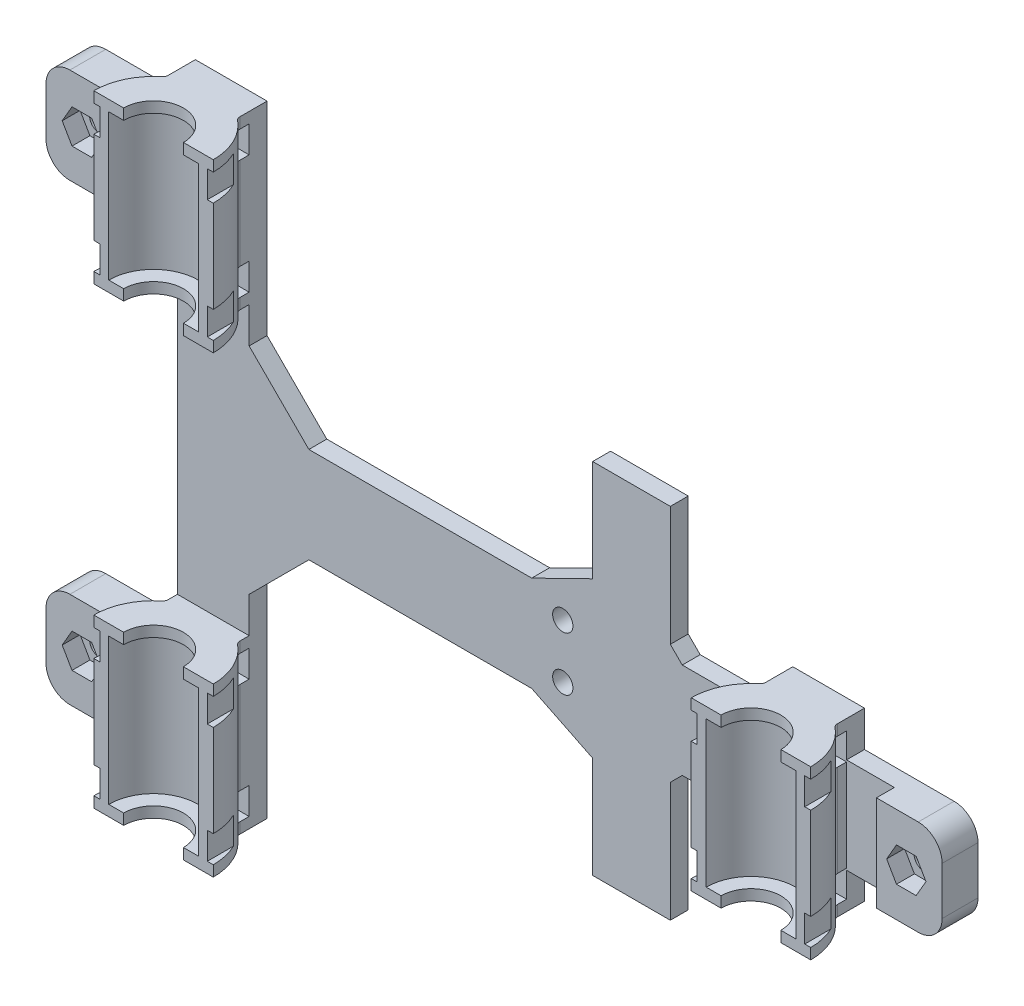
SolidWorks part; units mm, degrees
ref_plane "前视基准面" through (0, 0, 0) normal (0, 0, 1) x (1, 0, 0)
ref_plane "上视基准面" through (0, 0, 0) normal (0, 1, 0) x (1, 0, 0)
ref_plane "右视基准面" through (0, 0, 0) normal (1, 0, 0) x (0, 0, -1)
sketch "草图1" plane through (0, 0, 0) normal (0, 0, 1) x (1, 0, 0)
  line L1 (75, -70) -> (-75, -70)
  line L2 (75, -70) -> (75, 70)
  line L3 (75, 70) -> (-75, 70)
  line L4 (-75, -70) -> (-75, 70)
  line L5 (75, -70) -> (-75, 70) construction
  line L6 (75, 70) -> (-75, -70) construction
  point P0 (0, 0)
  dimension "D1" = 150
  dimension "D2" = 140
extrude "凸台-拉伸1" add sketch "草图1" along normal blind 3
sketch "草图2" plane through (0, 0, 0) normal (0, 1, 0) x (1, 0, 0)
  line L0 (-1000, 0) -> (49000, 0) construction
  line L1 (-999.3205, -17) -> (49000.6795, -17) construction
  line L2 (0, -1000) -> (0, 49000) construction
  line L3 (-57.5, -13) -> (-60, -13)
  line L4 (-42.5, -13) -> (-40, -13)
  line L5 (-55, -13) -> (-57.5, -13)
  line L6 (-45, -13) -> (-42.5, -13)
  line L7 (-50, -1013) -> (-50, 48987) construction
  line L8 (-56, -5) -> (-56, -3)
  line L9 (-75, -3) -> (75, -3) construction
  line L10 (-44, -5) -> (-44, -3)
  line L11 (-56, -3) -> (-44, -3)
  line L12 (56, -3) -> (44, -3)
  line L13 (44, -5) -> (44, -3)
  line L14 (56, -5) -> (56, -3)
  line L15 (45, -13) -> (42.5, -13)
  line L16 (55, -13) -> (57.5, -13)
  line L17 (42.5, -13) -> (40, -13)
  line L18 (57.5, -13) -> (60, -13)
  line L19 (75, -3) -> (-75, -3) construction
  circle A0 centre (50, -13) radius 4 construction
  circle A1 centre (-50, -13) radius 4 construction
  circle A2 centre (-50, -13) radius 7.5 construction
  circle A3 centre (50, -13) radius 7.5 construction
  arc A4 (-57.5, -13) -> (-42.5, -13) centre (-50, -13) cw
  arc A5 (-60, -13) -> (-40, -13) centre (-50, -13) cw
  arc A6 (-55, -13) -> (-45, -13) centre (-50, -13) cw
  arc A7 (55, -13) -> (45, -13) centre (50, -13) ccw
  arc A8 (60, -13) -> (40, -13) centre (50, -13) ccw
  arc A9 (57.5, -13) -> (42.5, -13) centre (50, -13) ccw
  dimension "D3" = 10
  dimension "D2" = 15
  dimension "D4" = 5
  dimension "D6" = 8
  dimension "D1" = 17
  dimension "D5" = 12
  dimension "D7" = 100
  dimension "D8" = 14
extrude "凸台-拉伸2" add sketch "草图2" along normal blind 14 and the other way blind 14 contours A8 L14 L12 L13 | A9 L18 A8 L17 | A8 L12 L13 region at (54.5317, 0, 3.5881) region at (45.4683, 0, 3.5881) region at (53.0916, 0, 3.7253)
extrude "凸台-拉伸3" add sketch "草图2<3>" along normal blind 14 and the other way blind 14 from offset 38 contours L8 A5 L10 L11 | A5 L3 A4 L4 | L8 A5 L11 region at (-58.75, 0, 12.7764) region at (-54.5317, 0, 3.5881) region at (-45.4683, 0, 3.5881)
sketch "草图2<3>" plane through (0, 0, 0) normal (0, 1, 0) x (1, 0, 0) same geometry as "草图2"
extrude "凸台-拉伸5" add sketch "草图2<4>" against normal blind 1.8 from vertex contours L5 A6 L6 A4 region at (-50, 0, 5.6677) starting at point (-42.5, 52, 13)
sketch "草图2<4>" plane through (0, 0, 0) normal (0, 1, 0) x (1, 0, 0) same geometry as "草图2"
extrude "凸台-拉伸6" add sketch "草图2<5>" along normal blind 1.8 from vertex contours L5 A6 L6 A4 region at (-50, 0, 5.6677) starting at point (-42.5, 24, 13)
sketch "草图2<5>" plane through (0, 0, 0) normal (0, 1, 0) x (1, 0, 0) same geometry as "草图2"
extrude "凸台-拉伸7" add sketch "草图2<6>" against normal blind 1.8 from vertex contours L16 A9 L15 A7 region at (56.25, 0, 12.8323) starting at point (42.5, 14, 13)
sketch "草图2<6>" plane through (0, 0, 0) normal (0, 1, 0) x (1, 0, 0) same geometry as "草图2"
mirror "镜向5" about plane through (0, 0, 0) normal (0, 1, 0) of "凸台-拉伸3"
extrude "凸台-拉伸8" add sketch "草图2<7>" along normal blind 1.8 from vertex contours L16 A9 L15 A7 region at (56.25, 0, 12.8323) starting at point (42.5, -14, 13)
sketch "草图2<7>" plane through (0, 0, 0) normal (0, 1, 0) x (1, 0, 0) same geometry as "草图2"
extrude "凸台-拉伸9" add sketch "草图2<8>" along normal blind 1.8 from vertex contours L5 A6 L6 A4 region at (-50, 0, 5.6677) starting at point (-57.5, -52, 13)
sketch "草图2<8>" plane through (0, 0, 0) normal (0, 1, 0) x (1, 0, 0) same geometry as "草图2"
extrude "凸台-拉伸10" add sketch "草图2<9>" against normal blind 1.8 from vertex contours L5 A6 L6 A4 region at (-50, 0, 5.6677) starting at point (-57.5, -24, 13)
sketch "草图2<9>" plane through (0, 0, 0) normal (0, 1, 0) x (1, 0, 0) same geometry as "草图2"
sketch "草图3" plane through (0, 0, 3) normal (0, 0, 1) x (1, 0, 0)
  line L0 (-56, 52) -> (-56, 46)
  line L1 (-56, -52) -> (-44, -52)
  line L2 (-44, -52) -> (-44, -24)
  line L3 (-44, 24) -> (-44, 18)
  line L4 (56, -14) -> (56, -8)
  line L5 (-44, -24) -> (-44, -18)
  line L6 (-44, 24) -> (-44, 52)
  line L7 (-44, 52) -> (-56, 52)
  line L8 (-34, -8) -> (13.5, -8)
  line L9 (44, -14) -> (44, 14) construction
  line L10 (44, -8) -> (44, -14)
  line L11 (44, -14) -> (56, -14)
  line L12 (44, 8) -> (44, 14)
  line L13 (-34, 8) -> (13.5, 8)
  line L14 (-44, -18) -> (-34, -8)
  line L15 (-44, 18) -> (-34, 8)
  line L16 (13.5, 8) -> (13.5, -8)
  line L17 (26.5, 8) -> (26.5, -8)
  line L18 (20, -1000) -> (20, 49000) construction
  line L19 (-1000, 0) -> (49000, 0) construction
  line L20 (13.5, 8) -> (13.5, 30)
  line L21 (13.5, -30) -> (26.5, -30)
  line L22 (13.5, -30) -> (13.5, -8)
  line L23 (13.5, 30) -> (26.5, 30)
  line L24 (26.5, -30) -> (26.5, -8)
  line L25 (13.5, -30) -> (26.5, 30) construction
  line L26 (13.5, 30) -> (26.5, -30) construction
  line L27 (26.5, 8) -> (44, 8)
  line L28 (26.5, -8) -> (44, -8)
  line L29 (26.5, 8) -> (26.5, 30)
  line L30 (-1044, 38) -> (48956, 38) construction
  line L31 (-75, 70) -> (-75, -70) construction
  line L32 (-65.7091, 38) -> (-67.3546, 40.85)
  line L33 (-67.3546, 40.85) -> (-70.6454, 40.85)
  line L34 (-70.6454, 40.85) -> (-72.2909, 38)
  line L35 (-72.2909, 38) -> (-70.6454, 35.15)
  line L36 (-70.6454, 35.15) -> (-67.3546, 35.15)
  line L37 (-67.3546, 35.15) -> (-65.7091, 38)
  line L38 (-56, 46) -> (-71, 46)
  line L39 (-75, 42) -> (-75, 34)
  line L40 (-71, 30) -> (-56, 30)
  line L41 (-56, 30) -> (-56, -30)
  line L42 (-71, -30) -> (-56, -30)
  line L43 (-75, -42) -> (-75, -34)
  line L44 (-56, -46) -> (-71, -46)
  line L45 (-67.3546, -35.15) -> (-65.7091, -38)
  line L46 (-70.6454, -35.15) -> (-67.3546, -35.15)
  line L47 (-72.2909, -38) -> (-70.6454, -35.15)
  line L48 (-70.6454, -40.85) -> (-72.2909, -38)
  line L49 (-67.3546, -40.85) -> (-70.6454, -40.85)
  line L50 (-65.7091, -38) -> (-67.3546, -40.85)
  line L51 (-56, -46) -> (-56, -52)
  line L52 (56, 8) -> (71, 8)
  line L53 (72.2909, 0) -> (70.6454, 2.85)
  line L54 (70.6454, 2.85) -> (67.3546, 2.85)
  line L55 (67.3546, 2.85) -> (65.7091, 0)
  line L56 (65.7091, 0) -> (67.3546, -2.85)
  line L57 (67.3546, -2.85) -> (70.6454, -2.85)
  line L58 (70.6454, -2.85) -> (72.2909, 0)
  line L59 (75, -70) -> (75, 70) construction
  line L60 (75, 4) -> (75, -4)
  line L61 (71, -8) -> (56, -8)
  line L62 (56, 8) -> (56, 14)
  line L63 (-64, 46) -> (-64, 30)
  line L64 (10.1454, 7.35) -> (11.7909, 4.5)
  line L65 (-64, -30) -> (-64, -46)
  line L66 (11.7909, -4.5) -> (10.1454, -1.65)
  line L67 (64, 8) -> (64, -8)
  line L68 (10.1454, -1.65) -> (6.8546, -1.65)
  line L69 (6.8546, -1.65) -> (5.2091, -4.5)
  line L70 (5.2091, -4.5) -> (6.8546, -7.35)
  line L71 (6.8546, -7.35) -> (10.1454, -7.35)
  line L72 (10.1454, -7.35) -> (11.7909, -4.5)
  line L73 (6.8546, 7.35) -> (10.1454, 7.35)
  line L74 (5.2091, 4.5) -> (6.8546, 7.35)
  line L75 (6.8546, 1.65) -> (5.2091, 4.5)
  line L76 (10.1454, 1.65) -> (6.8546, 1.65)
  line L77 (11.7909, 4.5) -> (10.1454, 1.65)
  line L78 (-40, -24) -> (-40, -52) construction
  line L79 (9.5, -62) -> (4.5, -62) construction
  line L80 (3.2458, 8) -> (3.2458, -8)
  line L81 (9.5, -62) -> (9.5, -19) construction
  line L82 (9.5, -19) -> (4.5, -19) construction
  line L83 (4.5, -62) -> (4.5, -19) construction
  line L84 (4.5, -40) -> (9.5, -40) construction
  circle A0 centre (-69, 38) radius 1.7
  circle A1 centre (-69, 38) radius 2.85 construction
  circle A2 centre (-69, -38) radius 2.85 construction
  circle A3 centre (-69, -38) radius 1.7
  circle A4 centre (69, 0) radius 1.7
  circle A5 centre (69, 0) radius 2.85 construction
  arc A6 (75, -4) -> (71, -8) centre (71, -4) cw
  arc A7 (71, 8) -> (75, 4) centre (71, 4) cw
  arc A8 (-71, -30) -> (-75, -34) centre (-71, -34) ccw
  arc A9 (-75, -42) -> (-71, -46) centre (-71, -42) ccw
  arc A10 (-75, 34) -> (-71, 30) centre (-71, 34) ccw
  arc A11 (-71, 46) -> (-75, 42) centre (-71, 42) ccw
  circle A12 centre (8.5, -4.5) radius 1.7
  circle A13 centre (8.5, -4.5) radius 2.85 construction
  circle A14 centre (8.5, 4.5) radius 2.85 construction
  circle A15 centre (8.5, 4.5) radius 1.7
  point P2 (-44, 8)
  point P7 (-44, -8)
  point P23 (20, 0)
  point P33 (-44, 38)
  point P90 (75, -8)
  point P93 (75, 8)
  point P96 (-75, -30)
  point P99 (-75, -46)
  point P102 (-75, 30)
  point P105 (-75, 46)
  line M11 (-44, 52) -> (-44, 24)
  line M13 (-56, 24) -> (-56, 52)
  line M14 (-56, 52) -> (-44, 52)
  line M15 (-75, 70) -> (-75, -70)
  line M16 (-75, -70) -> (75, -70)
  line M17 (75, -70) -> (75, 70)
  line M18 (75, 70) -> (-75, 70)
  line M19 (56, 14) -> (56, -14)
  line M20 (56, -14) -> (44, -14)
  line M21 (44, -14) -> (44, 14)
  line M22 (44, 14) -> (56, 14)
  line M23 (-56, -52) -> (-56, -24)
  line M25 (-44, -24) -> (-44, -52)
  line M26 (-44, -52) -> (-56, -52)
  dimension "D7" = 3.4
  dimension "D13" = 5.7
  dimension "D15" = 8
  dimension "D18" = 5
  dimension "D20" = 5
  dimension "D3" = 13
  dimension "D9" = 5.7
  dimension "D12" = 3.4
  dimension "D17" = 4
  dimension "D21" = 5.7
  dimension "D22" = 16.7542
  dimension "D6" = 3.4
  dimension "D2" = 20
  dimension "D8" = 13
  dimension "D10" = 8
  dimension "D11" = 8
  dimension "D14" = 13
  dimension "D16" = 8
  dimension "D19" = 5
  dimension "D23" = 11.5
  dimension "D24" = 9
  dimension "D25" = 60
  dimension "D26" = 5
  dimension "D27" = 4
  dimension "D28" = 43
  dimension "D29" = 4.5
  dimension "D30" = 44.5
  dimension "D31" = 21
  dimension "D32" = 10
  dimension "D33" = 10
fillet "圆角1" radius 1 6 edges at (44, 0, 5) (56, 0, 5) (-44, -38, 5) (-56, -38, 5) (-56, 38, 5) (-44, 38, 5)
sketch "草图5" plane through (0, 0, 13) normal (0, 0, 1) x (1, 0, 0)
  line L0 (-1000, 0) -> (49000, 0) construction
  line L1 (60, 7.7) -> (59, 7.7)
  line L2 (60, 7.7) -> (60, 12.2)
  line L3 (60, 12.2) -> (59, 12.2)
  line L4 (59, 7.7) -> (59, 12.2)
  line L5 (-1060, 38) -> (48940, 38) construction
  line L6 (-60, 24) -> (-60, 52) construction
  line L7 (59, -7.7) -> (59, -12.2)
  line L8 (60, -12.2) -> (59, -12.2)
  line L9 (60, -7.7) -> (60, -12.2)
  line L10 (60, -7.7) -> (59, -7.7)
  line L11 (60, -14) -> (60, 14) construction
  line L12 (-60, 50.2) -> (-59, 50.2)
  line L13 (-60, 50.2) -> (-60, 45.7)
  line L14 (-60, 45.7) -> (-59, 45.7)
  line L15 (-59, 50.2) -> (-59, 45.7)
  line L16 (-59, 25.8) -> (-59, 30.3)
  line L17 (-60, 30.3) -> (-59, 30.3)
  line L18 (-60, 25.8) -> (-60, 30.3)
  line L19 (-60, 25.8) -> (-59, 25.8)
  line L20 (-60, -25.8) -> (-59, -25.8)
  line L21 (-60, -25.8) -> (-60, -30.3)
  line L22 (-60, -30.3) -> (-59, -30.3)
  line L23 (-59, -25.8) -> (-59, -30.3)
  line L24 (-59, -50.2) -> (-59, -45.7)
  line L25 (-60, -45.7) -> (-59, -45.7)
  line L26 (-60, -50.2) -> (-60, -45.7)
  line L27 (-60, -50.2) -> (-59, -50.2)
  line L28 (-50, -986) -> (-50, 49014) construction
  line L29 (-56, 24) -> (-44, 24) construction
  line L30 (50, -1012) -> (50, 48988) construction
  line L31 (57.5, -12.2) -> (42.5, -12.2) construction
  line L32 (-40, -50.2) -> (-41, -50.2)
  line L33 (-40, -50.2) -> (-40, -45.7)
  line L34 (-40, -45.7) -> (-41, -45.7)
  line L35 (-41, -50.2) -> (-41, -45.7)
  line L36 (-41, -25.8) -> (-41, -30.3)
  line L37 (-40, -30.3) -> (-41, -30.3)
  line L38 (-40, -25.8) -> (-40, -30.3)
  line L39 (-40, -25.8) -> (-41, -25.8)
  line L40 (-40, 25.8) -> (-41, 25.8)
  line L41 (-40, 25.8) -> (-40, 30.3)
  line L42 (-40, 30.3) -> (-41, 30.3)
  line L43 (-41, 25.8) -> (-41, 30.3)
  line L44 (-41, 50.2) -> (-41, 45.7)
  line L45 (-40, 45.7) -> (-41, 45.7)
  line L46 (-40, 50.2) -> (-40, 45.7)
  line L47 (-40, 50.2) -> (-41, 50.2)
  line L48 (40, -7.7) -> (41, -7.7)
  line L49 (40, -7.7) -> (40, -12.2)
  line L50 (40, -12.2) -> (41, -12.2)
  line L51 (41, -7.7) -> (41, -12.2)
  line L52 (41, 7.7) -> (41, 12.2)
  line L53 (40, 12.2) -> (41, 12.2)
  line L54 (40, 7.7) -> (40, 12.2)
  line L55 (40, 7.7) -> (41, 7.7)
  point P12 (-60, 38)
  point P42 (-50, 24)
  point P47 (50, -12.2)
  dimension "D1" = 4.5
  dimension "D3" = 1
  dimension "D4" = 4.5
  dimension "D5" = 1
extrude "切除-拉伸5" cut sketch "草图5" against normal up to next
extrude "切除-拉伸6" cut sketch "草图3" against normal up to next contours L52 L38 L3 L15 L13 L20 L23 L29 L27 M19 M17 M18 M15 M13 M14 M11 M21 M22 | L42 L41 L40 M15 M23 M13 | L61 L28 L24 L21 L22 L8 L14 L5 L44 M17 M19 M20 M21 M25 M26 M23 M15 M16 region at (8.6816, 41.9347, 3) region at (-65.5515, 0, 3) region at (8.6816, -41.9347, 3)
extrude "切除-拉伸7" cut sketch "草图3<9>" against normal blind 10 contours A0 | A3 | A4 | A12 | A15 region at (-69, 38, 3) region at (-69, -38, 3) region at (69, 0, 3) region at (8.5, -4.5, 3) region at (8.5, 4.5, 3)
sketch "草图3<9>" plane through (0, 0, 3) normal (0, 0, 1) x (1, 0, 0) same geometry as "草图3"
extrude "凸台-拉伸11" add sketch "草图3<12>" along normal blind 3 contours A9 L44 L42 A8 L45 L50 L49 L48 L47 L46 M15 | L38 A11 A10 L40 L37 L36 L35 L34 L33 L32 M15 | L27 L17 L28 L72 L71 L70 L69 L68 L66 | A7 L52 L67 L61 A6 L58 L57 L56 L55 L54 L53 M17 region at (64.1942, 0, 3) region at (-64.1942, 38, 3) region at (8.3066, 0, 3) region at (-73.6911, -31.3089, 3)
sketch "草图3<12>" plane through (0, 0, 3) normal (0, 0, 1) x (1, 0, 0) same geometry as "草图3"
sketch "草图6" plane through (75, 0, 0) normal (1, 0, 0) x (0, 0, -1)
  line L0 (-1014.5151, 38) -> (48985.4849, 38) construction
  line L1 (-13, 50.2) -> (-8.6411, 50.2) construction
  line L2 (-3, 45.7) -> (-5, 45.7)
  line L3 (-3, 45.7) -> (-3, 50.2)
  line L4 (-3, 50.2) -> (-5, 50.2)
  line L5 (-1000, 0) -> (49000, 0) construction
  line L6 (0, -4) -> (0, 4) construction
  line L7 (-3, 7.7) -> (-5, 7.7)
  line L8 (-3, 7.7) -> (-3, 12.2)
  line L9 (-3, 12.2) -> (-5, 12.2)
  line L10 (-5, 7.7) -> (-5, 12.2)
  line L11 (-5, 45.7) -> (-5, 50.2)
  line L12 (-5, -7.7) -> (-5, -12.2)
  line L13 (-3, -12.2) -> (-5, -12.2)
  line L14 (-3, -7.7) -> (-3, -12.2)
  line L15 (-3, -7.7) -> (-5, -7.7)
  line L16 (-8.6411, 45.7) -> (-13, 45.7) construction
  line L17 (-3, 8) -> (-3, 30) construction
  line L18 (-5, 30.3) -> (-5, 25.8)
  line L19 (-3, 25.8) -> (-5, 25.8)
  line L20 (-3, 30.3) -> (-3, 25.8)
  line L21 (-3, 30.3) -> (-5, 30.3)
  line L22 (-3, -30.3) -> (-5, -30.3)
  line L23 (-3, -30.3) -> (-3, -25.8)
  line L24 (-3, -25.8) -> (-5, -25.8)
  line L25 (-5, -30.3) -> (-5, -25.8)
  line L26 (-5, -45.7) -> (-5, -50.2)
  line L27 (-3, -50.2) -> (-5, -50.2)
  line L28 (-3, -45.7) -> (-3, -50.2)
  line L29 (-3, -45.7) -> (-5, -45.7)
  point P12 (0, 0)
  dimension "D1" = 2
  dimension "D2" = 2
  dimension "D4" = 38
extrude "切除-拉伸8" cut sketch "草图6" against normal blind 20 from offset 15 contours L10 L7 L8 L9 | L14 L15 L12 L13 region at (75, 9.95, 4) region at (75, -9.95, 4) offset against normal yes
extrude "切除-拉伸9" cut sketch "草图6<3>" against normal blind 20 from offset 115 contours L11 L2 L3 L4 | L20 L21 L18 L19 | L25 L22 L23 L24 | L28 L29 L26 L27 region at (75, 47.95, 4) region at (75, 28.05, 4) region at (75, -28.05, 4) region at (75, -47.95, 4) offset against normal yes
sketch "草图6<3>" plane through (75, 0, 0) normal (1, 0, 0) x (0, 0, -1) same geometry as "草图6"
chamfer "倒角2" distance 2 angle 45 4 edges at (44, -8, 1.5) (44, 8, 1.5) (26.5, 8, 1.5) (26.5, -8, 1.5)
fillet "圆角2" radius 4 12 edges at (43.8744, -9.95, 5) (43.8744, 9.95, 5) (56.1256, 9.95, 5) (56.1256, -9.95, 5) (-43.8744, -28.05, 5) (-43.8744, -47.95, 5) (-56.1256, -28.05, 5) (-56.1256, -47.95, 5) (-56.1256, 28.05, 5) (-43.8744, 28.05, 5) (-43.8744, 47.95, 5) (-56.1256, 47.95, 5)
extrude "凸台-拉伸12" add sketch "草图3<13>" along normal blind 24 contours L17 L29 L23 L20 L16 L22 L21 L24 region at (20, 0, 3)
sketch "草图3<13>" plane through (0, 0, 3) normal (0, 0, 1) x (1, 0, 0) same geometry as "草图3"
sketch "草图7" plane through (13.5, 0, 0) normal (-1, 0, 0) x (0, 0, 1)
  line L0 (21, -6) -> (19, -6)
  line L1 (0, 30) -> (27, 30) construction
  line L2 (19, 30) -> (21, 30)
  line L3 (19, 30) -> (19, -30)
  line L4 (19, -30) -> (21, -30)
  line L5 (19, 6) -> (21, 6)
  line L7 (21, 30) -> (21, 29.99)
  line L8 (0, -30) -> (27, -30) construction
  line L9 (20.75, 29.74) -> (20.05, 29.74)
  line L10 (19.8, 29.49) -> (19.8, 29.19)
  line L11 (-1000, 0) -> (49000, 0) construction
  line L12 (20.05, 28.94) -> (20.75, 28.94)
  line L13 (21, 28.69) -> (21, -30)
  line L14 (20.75, 27.74) -> (20.05, 27.74)
  line L15 (19.8, 27.49) -> (19.8, 27.19)
  line L16 (20.05, 26.94) -> (20.75, 26.94)
  line L17 (20.75, 25.74) -> (20.05, 25.74)
  line L18 (19.8, 25.49) -> (19.8, 25.19)
  line L19 (20.05, 24.94) -> (20.75, 24.94)
  line L20 (20.75, 23.74) -> (20.05, 23.74)
  line L21 (19.8, 23.49) -> (19.8, 23.19)
  line L22 (20.05, 22.94) -> (20.75, 22.94)
  line L23 (20.75, 21.74) -> (20.05, 21.74)
  line L24 (19.8, 21.49) -> (19.8, 21.19)
  line L25 (20.05, 20.94) -> (20.75, 20.94)
  line L26 (20.75, 19.74) -> (20.05, 19.74)
  line L27 (19.8, 19.49) -> (19.8, 19.19)
  line L28 (20.05, 18.94) -> (20.75, 18.94)
  line L29 (20.75, 17.74) -> (20.05, 17.74)
  line L30 (19.8, 17.49) -> (19.8, 17.19)
  line L31 (20.05, 16.94) -> (20.75, 16.94)
  line L32 (20.75, 15.74) -> (20.05, 15.74)
  line L33 (19.8, 15.49) -> (19.8, 15.19)
  line L34 (20.05, 14.94) -> (20.75, 14.94)
  line L35 (20.75, 13.74) -> (20.05, 13.74)
  line L36 (19.8, 13.49) -> (19.8, 13.19)
  line L37 (20.05, 12.94) -> (20.75, 12.94)
  line L38 (20.75, 11.74) -> (20.05, 11.74)
  line L39 (19.8, 11.49) -> (19.8, 11.19)
  line L40 (20.05, 10.94) -> (20.75, 10.94)
  line L41 (20.75, 9.74) -> (20.05, 9.74)
  line L42 (19.8, 9.49) -> (19.8, 9.19)
  line L43 (20.05, 8.94) -> (20.75, 8.94)
  line L44 (20.75, 7.74) -> (20.05, 7.74)
  line L45 (19.8, 7.49) -> (19.8, 7.19)
  line L46 (20.05, 6.94) -> (20.75, 6.94)
  line L47 (20.75, 5.74) -> (20.05, 5.74)
  line L48 (19.8, 5.49) -> (19.8, 5.19)
  line L49 (20.05, 4.94) -> (20.75, 4.94)
  line L50 (20.75, 3.74) -> (20.05, 3.74)
  line L51 (19.8, 3.49) -> (19.8, 3.19)
  line L52 (20.05, 2.94) -> (20.75, 2.94)
  line L53 (20.75, 1.74) -> (20.05, 1.74)
  line L54 (19.8, 1.49) -> (19.8, 1.19)
  line L55 (20.05, 0.94) -> (20.75, 0.94)
  line L56 (20.75, -0.26) -> (20.05, -0.26)
  line L57 (19.8, -0.51) -> (19.8, -0.81)
  line L58 (20.05, -1.06) -> (20.75, -1.06)
  line L59 (20.75, -2.26) -> (20.05, -2.26)
  line L60 (19.8, -2.51) -> (19.8, -2.81)
  line L61 (20.05, -3.06) -> (20.75, -3.06)
  line L62 (20.75, -4.26) -> (20.05, -4.26)
  line L63 (19.8, -4.51) -> (19.8, -4.81)
  line L64 (20.05, -5.06) -> (20.75, -5.06)
  line L65 (20.75, -6.26) -> (20.05, -6.26)
  line L66 (19.8, -6.51) -> (19.8, -6.81)
  line L67 (20.05, -7.06) -> (20.75, -7.06)
  line L68 (20.75, -8.26) -> (20.05, -8.26)
  line L69 (19.8, -8.51) -> (19.8, -8.81)
  line L70 (20.05, -9.06) -> (20.75, -9.06)
  line L71 (20.75, -10.26) -> (20.05, -10.26)
  line L72 (19.8, -10.51) -> (19.8, -10.81)
  line L73 (20.05, -11.06) -> (20.75, -11.06)
  line L74 (20.75, -12.26) -> (20.05, -12.26)
  line L75 (19.8, -12.51) -> (19.8, -12.81)
  line L76 (20.05, -13.06) -> (20.75, -13.06)
  line L77 (20.75, -14.26) -> (20.05, -14.26)
  line L78 (19.8, -14.51) -> (19.8, -14.81)
  line L79 (20.05, -15.06) -> (20.75, -15.06)
  line L80 (20.75, -16.26) -> (20.05, -16.26)
  line L81 (19.8, -16.51) -> (19.8, -16.81)
  line L82 (20.05, -17.06) -> (20.75, -17.06)
  line L83 (20.75, -18.26) -> (20.05, -18.26)
  line L84 (19.8, -18.51) -> (19.8, -18.81)
  line L85 (20.05, -19.06) -> (20.75, -19.06)
  line L86 (20.75, -20.26) -> (20.05, -20.26)
  line L87 (19.8, -20.51) -> (19.8, -20.81)
  line L88 (20.05, -21.06) -> (20.75, -21.06)
  line L89 (20.75, -22.26) -> (20.05, -22.26)
  line L90 (19.8, -22.51) -> (19.8, -22.81)
  line L91 (20.05, -23.06) -> (20.75, -23.06)
  line L92 (20.75, -24.26) -> (20.05, -24.26)
  line L93 (19.8, -24.51) -> (19.8, -24.81)
  line L94 (20.05, -25.06) -> (20.75, -25.06)
  line L95 (20.75, -26.26) -> (20.05, -26.26)
  line L96 (19.8, -26.51) -> (19.8, -26.81)
  line L97 (20.05, -27.06) -> (20.75, -27.06)
  line L98 (20.75, -28.26) -> (20.05, -28.26)
  line L99 (19.8, -28.51) -> (19.8, -28.81)
  line L100 (20.05, -29.06) -> (20.75, -29.06)
  line L101 (27, -30) -> (27, 30) construction
  line L102 (21, 28.69) -> (21, 29.99)
  arc A0 (20.05, 29.74) -> (19.8, 29.49) centre (20.05, 29.49) ccw
  arc A1 (19.8, 29.19) -> (20.05, 28.94) centre (20.05, 29.19) ccw
  arc A2 (20.75, 28.94) -> (21, 28.69) centre (20.75, 28.69) cw
  arc A3 (20.75, 29.74) -> (21, 29.99) centre (20.75, 29.99) ccw
  arc A4 (20.05, 27.74) -> (19.8, 27.49) centre (20.05, 27.49) ccw
  arc A5 (19.8, 27.19) -> (20.05, 26.94) centre (20.05, 27.19) ccw
  arc A6 (20.75, 27.74) -> (21, 27.99) centre (20.75, 27.99) ccw
  arc A7 (20.75, 26.94) -> (21, 26.69) centre (20.75, 26.69) cw
  arc A8 (20.05, 25.74) -> (19.8, 25.49) centre (20.05, 25.49) ccw
  arc A9 (19.8, 25.19) -> (20.05, 24.94) centre (20.05, 25.19) ccw
  arc A10 (20.75, 25.74) -> (21, 25.99) centre (20.75, 25.99) ccw
  arc A11 (20.75, 24.94) -> (21, 24.69) centre (20.75, 24.69) cw
  arc A12 (20.05, 23.74) -> (19.8, 23.49) centre (20.05, 23.49) ccw
  arc A13 (19.8, 23.19) -> (20.05, 22.94) centre (20.05, 23.19) ccw
  arc A14 (20.75, 23.74) -> (21, 23.99) centre (20.75, 23.99) ccw
  arc A15 (20.75, 22.94) -> (21, 22.69) centre (20.75, 22.69) cw
  arc A16 (20.05, 21.74) -> (19.8, 21.49) centre (20.05, 21.49) ccw
  arc A17 (19.8, 21.19) -> (20.05, 20.94) centre (20.05, 21.19) ccw
  arc A18 (20.75, 21.74) -> (21, 21.99) centre (20.75, 21.99) ccw
  arc A19 (20.75, 20.94) -> (21, 20.69) centre (20.75, 20.69) cw
  arc A20 (20.05, 19.74) -> (19.8, 19.49) centre (20.05, 19.49) ccw
  arc A21 (19.8, 19.19) -> (20.05, 18.94) centre (20.05, 19.19) ccw
  arc A22 (20.75, 19.74) -> (21, 19.99) centre (20.75, 19.99) ccw
  arc A23 (20.75, 18.94) -> (21, 18.69) centre (20.75, 18.69) cw
  arc A24 (20.05, 17.74) -> (19.8, 17.49) centre (20.05, 17.49) ccw
  arc A25 (19.8, 17.19) -> (20.05, 16.94) centre (20.05, 17.19) ccw
  arc A26 (20.75, 17.74) -> (21, 17.99) centre (20.75, 17.99) ccw
  arc A27 (20.75, 16.94) -> (21, 16.69) centre (20.75, 16.69) cw
  arc A28 (20.05, 15.74) -> (19.8, 15.49) centre (20.05, 15.49) ccw
  arc A29 (19.8, 15.19) -> (20.05, 14.94) centre (20.05, 15.19) ccw
  arc A30 (20.75, 15.74) -> (21, 15.99) centre (20.75, 15.99) ccw
  arc A31 (20.75, 14.94) -> (21, 14.69) centre (20.75, 14.69) cw
  arc A32 (20.05, 13.74) -> (19.8, 13.49) centre (20.05, 13.49) ccw
  arc A33 (19.8, 13.19) -> (20.05, 12.94) centre (20.05, 13.19) ccw
  arc A34 (20.75, 13.74) -> (21, 13.99) centre (20.75, 13.99) ccw
  arc A35 (20.75, 12.94) -> (21, 12.69) centre (20.75, 12.69) cw
  arc A36 (20.05, 11.74) -> (19.8, 11.49) centre (20.05, 11.49) ccw
  arc A37 (19.8, 11.19) -> (20.05, 10.94) centre (20.05, 11.19) ccw
  arc A38 (20.75, 11.74) -> (21, 11.99) centre (20.75, 11.99) ccw
  arc A39 (20.75, 10.94) -> (21, 10.69) centre (20.75, 10.69) cw
  arc A40 (20.05, 9.74) -> (19.8, 9.49) centre (20.05, 9.49) ccw
  arc A41 (19.8, 9.19) -> (20.05, 8.94) centre (20.05, 9.19) ccw
  arc A42 (20.75, 9.74) -> (21, 9.99) centre (20.75, 9.99) ccw
  arc A43 (20.75, 8.94) -> (21, 8.69) centre (20.75, 8.69) cw
  arc A44 (20.05, 7.74) -> (19.8, 7.49) centre (20.05, 7.49) ccw
  arc A45 (19.8, 7.19) -> (20.05, 6.94) centre (20.05, 7.19) ccw
  arc A46 (20.75, 7.74) -> (21, 7.99) centre (20.75, 7.99) ccw
  arc A47 (20.75, 6.94) -> (21, 6.69) centre (20.75, 6.69) cw
  arc A48 (20.05, 5.74) -> (19.8, 5.49) centre (20.05, 5.49) ccw
  arc A49 (19.8, 5.19) -> (20.05, 4.94) centre (20.05, 5.19) ccw
  arc A50 (20.75, 5.74) -> (21, 5.99) centre (20.75, 5.99) ccw
  arc A51 (20.75, 4.94) -> (21, 4.69) centre (20.75, 4.69) cw
  arc A52 (20.05, 3.74) -> (19.8, 3.49) centre (20.05, 3.49) ccw
  arc A53 (19.8, 3.19) -> (20.05, 2.94) centre (20.05, 3.19) ccw
  arc A54 (20.75, 3.74) -> (21, 3.99) centre (20.75, 3.99) ccw
  arc A55 (20.75, 2.94) -> (21, 2.69) centre (20.75, 2.69) cw
  arc A56 (20.05, 1.74) -> (19.8, 1.49) centre (20.05, 1.49) ccw
  arc A57 (19.8, 1.19) -> (20.05, 0.94) centre (20.05, 1.19) ccw
  arc A58 (20.75, 1.74) -> (21, 1.99) centre (20.75, 1.99) ccw
  arc A59 (20.75, 0.94) -> (21, 0.69) centre (20.75, 0.69) cw
  arc A60 (20.05, -0.26) -> (19.8, -0.51) centre (20.05, -0.51) ccw
  arc A61 (19.8, -0.81) -> (20.05, -1.06) centre (20.05, -0.81) ccw
  arc A62 (20.75, -0.26) -> (21, -0.01) centre (20.75, -0.01) ccw
  arc A63 (20.75, -1.06) -> (21, -1.31) centre (20.75, -1.31) cw
  arc A64 (20.05, -2.26) -> (19.8, -2.51) centre (20.05, -2.51) ccw
  arc A65 (19.8, -2.81) -> (20.05, -3.06) centre (20.05, -2.81) ccw
  arc A66 (20.75, -2.26) -> (21, -2.01) centre (20.75, -2.01) ccw
  arc A67 (20.75, -3.06) -> (21, -3.31) centre (20.75, -3.31) cw
  arc A68 (20.05, -4.26) -> (19.8, -4.51) centre (20.05, -4.51) ccw
  arc A69 (19.8, -4.81) -> (20.05, -5.06) centre (20.05, -4.81) ccw
  arc A70 (20.75, -4.26) -> (21, -4.01) centre (20.75, -4.01) ccw
  arc A71 (20.75, -5.06) -> (21, -5.31) centre (20.75, -5.31) cw
  arc A72 (20.05, -6.26) -> (19.8, -6.51) centre (20.05, -6.51) ccw
  arc A73 (19.8, -6.81) -> (20.05, -7.06) centre (20.05, -6.81) ccw
  arc A74 (20.75, -6.26) -> (21, -6.01) centre (20.75, -6.01) ccw
  arc A75 (20.75, -7.06) -> (21, -7.31) centre (20.75, -7.31) cw
  arc A76 (20.05, -8.26) -> (19.8, -8.51) centre (20.05, -8.51) ccw
  arc A77 (19.8, -8.81) -> (20.05, -9.06) centre (20.05, -8.81) ccw
  arc A78 (20.75, -8.26) -> (21, -8.01) centre (20.75, -8.01) ccw
  arc A79 (20.75, -9.06) -> (21, -9.31) centre (20.75, -9.31) cw
  arc A80 (20.05, -10.26) -> (19.8, -10.51) centre (20.05, -10.51) ccw
  arc A81 (19.8, -10.81) -> (20.05, -11.06) centre (20.05, -10.81) ccw
  arc A82 (20.75, -10.26) -> (21, -10.01) centre (20.75, -10.01) ccw
  arc A83 (20.75, -11.06) -> (21, -11.31) centre (20.75, -11.31) cw
  arc A84 (20.05, -12.26) -> (19.8, -12.51) centre (20.05, -12.51) ccw
  arc A85 (19.8, -12.81) -> (20.05, -13.06) centre (20.05, -12.81) ccw
  arc A86 (20.75, -12.26) -> (21, -12.01) centre (20.75, -12.01) ccw
  arc A87 (20.75, -13.06) -> (21, -13.31) centre (20.75, -13.31) cw
  arc A88 (20.05, -14.26) -> (19.8, -14.51) centre (20.05, -14.51) ccw
  arc A89 (19.8, -14.81) -> (20.05, -15.06) centre (20.05, -14.81) ccw
  arc A90 (20.75, -14.26) -> (21, -14.01) centre (20.75, -14.01) ccw
  arc A91 (20.75, -15.06) -> (21, -15.31) centre (20.75, -15.31) cw
  arc A92 (20.05, -16.26) -> (19.8, -16.51) centre (20.05, -16.51) ccw
  arc A93 (19.8, -16.81) -> (20.05, -17.06) centre (20.05, -16.81) ccw
  arc A94 (20.75, -16.26) -> (21, -16.01) centre (20.75, -16.01) ccw
  arc A95 (20.75, -17.06) -> (21, -17.31) centre (20.75, -17.31) cw
  arc A96 (20.05, -18.26) -> (19.8, -18.51) centre (20.05, -18.51) ccw
  arc A97 (19.8, -18.81) -> (20.05, -19.06) centre (20.05, -18.81) ccw
  arc A98 (20.75, -18.26) -> (21, -18.01) centre (20.75, -18.01) ccw
  arc A99 (20.75, -19.06) -> (21, -19.31) centre (20.75, -19.31) cw
  arc A100 (20.05, -20.26) -> (19.8, -20.51) centre (20.05, -20.51) ccw
  arc A101 (19.8, -20.81) -> (20.05, -21.06) centre (20.05, -20.81) ccw
  arc A102 (20.75, -20.26) -> (21, -20.01) centre (20.75, -20.01) ccw
  arc A103 (20.75, -21.06) -> (21, -21.31) centre (20.75, -21.31) cw
  arc A104 (20.05, -22.26) -> (19.8, -22.51) centre (20.05, -22.51) ccw
  arc A105 (19.8, -22.81) -> (20.05, -23.06) centre (20.05, -22.81) ccw
  arc A106 (20.75, -22.26) -> (21, -22.01) centre (20.75, -22.01) ccw
  arc A107 (20.75, -23.06) -> (21, -23.31) centre (20.75, -23.31) cw
  arc A108 (20.05, -24.26) -> (19.8, -24.51) centre (20.05, -24.51) ccw
  arc A109 (19.8, -24.81) -> (20.05, -25.06) centre (20.05, -24.81) ccw
  arc A110 (20.75, -24.26) -> (21, -24.01) centre (20.75, -24.01) ccw
  arc A111 (20.75, -25.06) -> (21, -25.31) centre (20.75, -25.31) cw
  arc A112 (20.05, -26.26) -> (19.8, -26.51) centre (20.05, -26.51) ccw
  arc A113 (19.8, -26.81) -> (20.05, -27.06) centre (20.05, -26.81) ccw
  arc A114 (20.75, -26.26) -> (21, -26.01) centre (20.75, -26.01) ccw
  arc A115 (20.75, -27.06) -> (21, -27.31) centre (20.75, -27.31) cw
  arc A116 (20.05, -28.26) -> (19.8, -28.51) centre (20.05, -28.51) ccw
  arc A117 (19.8, -28.81) -> (20.05, -29.06) centre (20.05, -28.81) ccw
  arc A118 (20.75, -28.26) -> (21, -28.01) centre (20.75, -28.01) ccw
  arc A119 (20.75, -29.06) -> (21, -29.31) centre (20.75, -29.31) cw
  point P21 (21, 28.94)
  point P24 (21, 29.74)
  line M6 (0, -30) -> (27, -30)
  dimension "D5" = 30
  dimension "D6" = 0.8
  dimension "D3" = 0.25
  dimension "D1" = 2
  dimension "D2" = 0.8
  dimension "D4" = 0.26
  dimension "D7" = 6
  dimension "D8" = 12
extrude "切除-拉伸10" cut sketch "草图7" against normal blind 10 contours L11 L3 L13 A119 L100 A117 L99 A116 L98 A118 A115 L97 A113 L96 A112 L95 A114 A111 L94 A109 L93 A108 L92 A110 A107 L91 A105 L90 A104 L89 A106 A103 L88 A101 L87 A100 L86 A102 A99 L85 A97 L84 A96 L83 A98 M6 | L41 A42 L13 A39 L40 A37 L39 A36 L38 A38 A35 L37 A33 L36 A32 L35 A34 A31 L34 A29 L33 A28 L32 A30 A27 L31 A25 L30 A24 L29 A26 A23 L28 A21 L27 A20 L26 A22 A19 L25 A17 L24 A16 L23 A18 region at (13.5, -18.1074, 19.8641) region at (13.5, 17.8926, 19.8641)
sketch "草图8" plane through (13.5, 0, 0) normal (-1, 0, 0) x (0, 0, 1)
  line L0 (27, -30) -> (27, 30) construction
  line L1 (19, 6) -> (27, 6)
  line L2 (19, 6) -> (19, 8.4)
  line L3 (19, 8.4) -> (27, 8.4)
  line L4 (27, 6) -> (27, 8.4)
  line L5 (-1000, 0) -> (49000, 0) construction
  line L6 (27, -6) -> (27, -8.4)
  line L7 (19, -8.4) -> (27, -8.4)
  line L8 (19, -6) -> (19, -8.4)
  line L9 (19, -6) -> (27, -6)
  dimension "D1" = 2.4
extrude "切除-拉伸11" cut sketch "草图8" against normal blind 10
chamfer "倒角1" distance 10.2 distance2 5 1 edges at (13.5, 8, 3) first distance on face at (-5.7514, 8, 3)
chamfer "倒角3" distance 5 distance2 10.2 1 edges at (13.5, -8, 3) first distance on face at (13.5, 0.8333, 11.8333)
sketch "草图9" plane through (0, -52, 0) normal (0, -1, 0) x (1, 0, 0)
  line L0 (-75, 0) -> (75, 0)
  line L1 (75, 0) -> (75, 13)
  line L2 (75, 13) -> (40, 13)
  line L3 (40, 13) -> (40, 3)
  line L4 (28.5, 3) -> (42, 3) construction
  line L5 (40, 3) -> (-40, 3)
  line L6 (-44, 3) -> (-34, 3) construction
  line L7 (-40, 3) -> (-40, 13)
  line L8 (-40, 13) -> (-75, 13)
  line L9 (-75, 13) -> (-75, 0)
extrude "切除-拉伸13" cut sketch "草图9" against normal through all flip side to cut contours L5 L7 L8 L9 L0 L1 L2 L3
